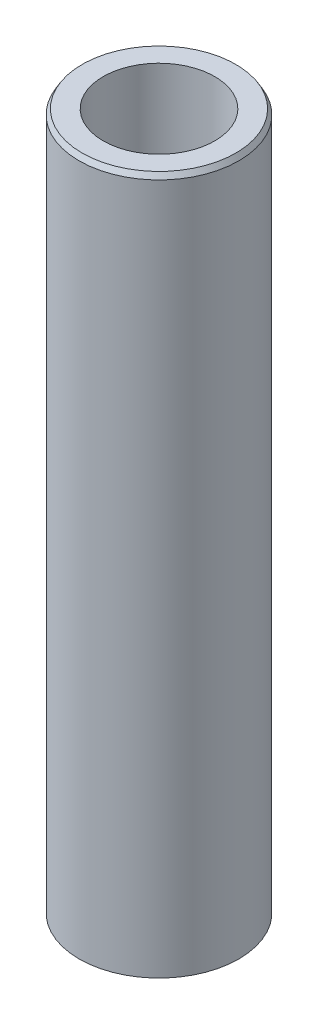
SolidWorks part; units mm, degrees
ref_plane "Front Plane" through (0, 0, 0) normal (0, 0, 1) x (1, 0, 0)
ref_plane "Top Plane" through (0, 0, 0) normal (0, 1, 0) x (1, 0, 0)
ref_plane "Right Plane" through (0, 0, 0) normal (1, 0, 0) x (0, 0, -1)
sketch "Sketch1" plane through (0, 0, 0) normal (0, 1, 0) x (1, 0, 0)
  circle A0 centre (0, 0) radius 57.5
  dimension "SHAFT_OD" = 115
extrude "Boss-Extrude1" add sketch "Sketch1" along normal blind 503.6492
sketch "Sketch2" plane through (0, 0, 0) normal (0, 1, 0) x (1, 0, 0)
  circle A0 centre (0, 0) radius 40.1594
  dimension "BORE_D" = 80.3188
extrude "Cut-Extrude1" cut sketch "Sketch2" along normal through all
chamfer "Chamfer1" distance 3.764 angle 30 2 edges at (0, 503.6492, 57.5) (0, 0, 57.5) first distance on face at (0, 503.6492, 57.5) first distance on face at (0, 0, 40.1594)
